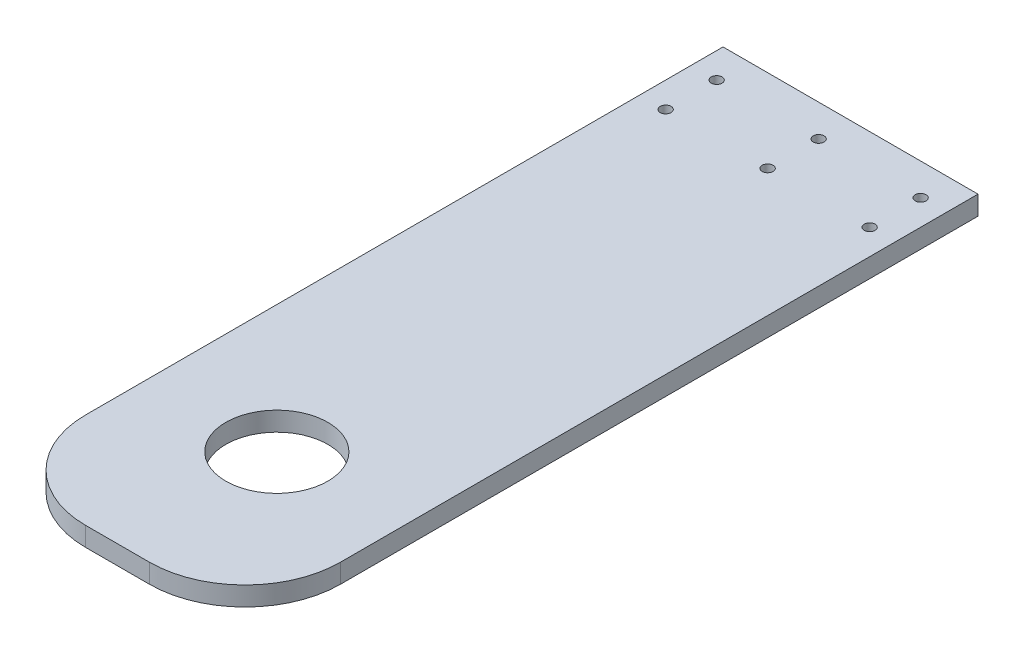
SolidWorks part; units mm, degrees
material "6061-T6 (SS)"
ref_plane "Front Plane" through (0, 0, 0) normal (0, 0, 1) x (1, 0, 0)
ref_plane "Top Plane" through (0, 0, 0) normal (0, 1, 0) x (1, 0, 0)
ref_plane "Right Plane" through (0, 0, 0) normal (1, 0, 0) x (0, 0, -1)
sketch "Sketch1" plane through (0, 0, 0) normal (0, 1, 0) x (1, 0, 0)
  line L1 (0, 0) -> (80, 0)
  line L2 (0, 0) -> (0, -230)
  line L3 (0, -230) -> (80, -230)
  line L4 (80, 0) -> (80, -230)
  dimension "D1" = 80
  dimension "D2" = 230
extrude "Boss-Extrude1" add sketch "Sketch1" along normal blind 6
sketch "Sketch5" plane through (0, 6, 0) normal (0, 1, 0) x (1, 0, 0)
  circle A1 centre (40, -180) radius 20
  point P1 (40, -180)
hole_wizard "Ø32.0 (32) Diameter Hole1" positions "Sketch5" profile "Sketch6" hole size "Ø32.0" standard "DIN" end condition through all
sketch "Sketch6" plane through (40, 6, 180) normal (1, 0, 0) x (0, 0, 1)
  line L0 (0, 0) -> (0, 6)
  line L1 (0, 6) -> (16, 6)
  line L2 (16, 6) -> (16, 0)
  line L5 (16, 0) -> (0, 0)
  line L11 (0, -6.35) -> (0, 107.95) construction
  dimension "Thru Hole Dia." = 32
  dimension "Thru Hole Depth" = 6
fillet "Fillet1" radius 30 2 edges at (0, 3, 230) (80, 3, 230)
sketch "Sketch9" plane through (0, 0, 0) normal (0, 1, 0) x (1, 0, 0)
  line L0 (40, 0) -> (40, -57.4233) construction
  line L1 (80, 0) -> (0, 0) construction
  point P0 (8, -10)
  point P6 (40, -10)
  point P7 (72, -10)
  point P8 (40, -26)
  point P9 (72, -26)
  point P10 (8, -26)
  point P17 (0, 0)
  dimension "D3" = 10
  dimension "D1" = 3
  dimension "D2" = 2
hole_wizard "CBORE for M3 Hex Socket Head Cap Screw1" positions "Sketch9" profile "Sketch8" counterbore size "M3" standard "DIN" end condition through all
sketch "Sketch8" plane through (8, 0, 10) normal (1, 0, 0) x (0, 0, -1)
  line L0 (0, 0) -> (0, 6)
  line L1 (0, 6) -> (1.7, 6)
  line L3 (1.7, 6) -> (1.7, 3.4)
  line L4 (1.7, 3.4) -> (3.25, 3.4)
  line L5 (3.25, 3.4) -> (3.25, 0)
  line L7 (3.25, 0) -> (0, 0)
  line L11 (0, -6.35) -> (0, 107.95) construction
  dimension "Thru Hole Dia." = 3.4
  dimension "Thru Hole Depth" = 6
  dimension "C'Bore Dia." = 6.5
  dimension "C'Bore Depth" = 3.4
